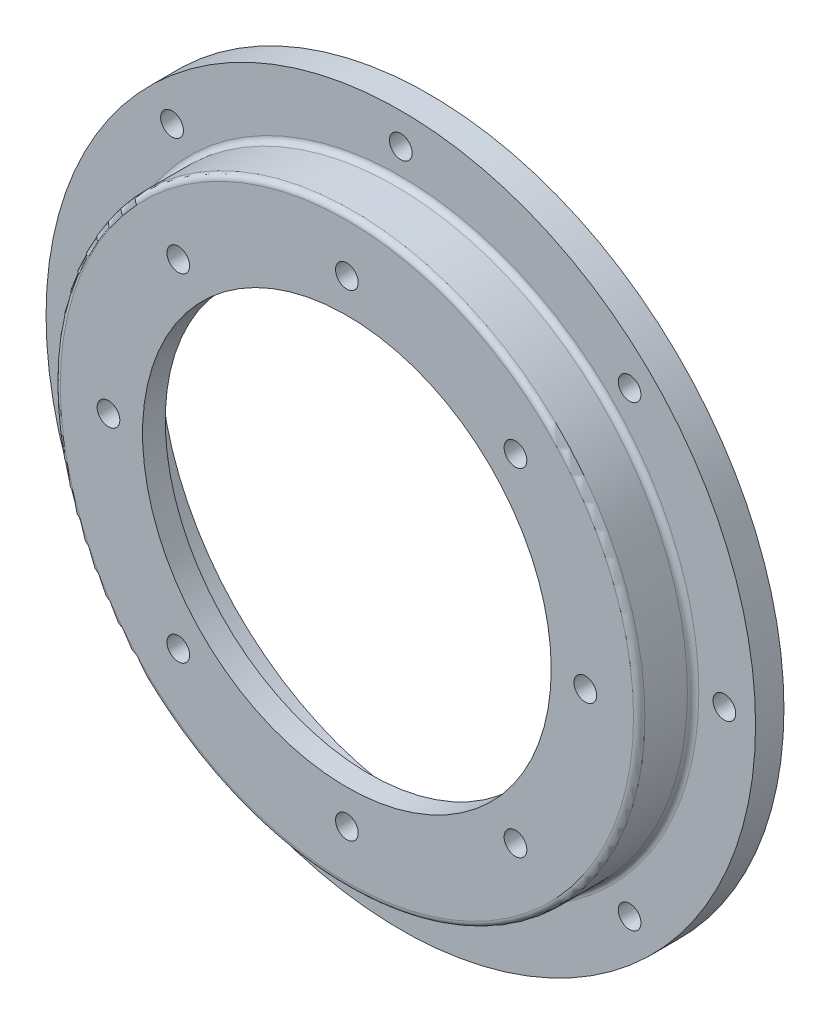
SolidWorks part; units mm, degrees
material "1.0503 (C45)"
ref_plane "Front Plane" through (0, 0, 0) normal (0, 0, 1) x (1, 0, 0)
ref_plane "Top Plane" through (0, 0, 0) normal (0, 1, 0) x (1, 0, 0)
ref_plane "Right Plane" through (0, 0, 0) normal (1, 0, 0) x (0, 0, -1)
sketch "Sketch1" plane through (0, 0, 0) normal (0, 0, 1) x (1, 0, 0)
  line L0 (0, 0) -> (0, 63.1981) construction
  circle A0 centre (0, 0) radius 62.5
  circle A1 centre (0, 0) radius 36
  circle A2 centre (0, 0) radius 51.5
  circle A3 centre (0, 0) radius 47.5
  point P2 (0, 57)
  point P3 (0, 42)
  point P5 (29.6985, 29.6985)
  point P6 (40.3051, 40.3051)
  point P8 (42, 0)
  point P9 (29.6985, -29.6985)
  point P10 (0, -42)
  point P11 (-29.6985, -29.6985)
  point P12 (-42, 0)
  point P13 (-29.6985, 29.6985)
  point P14 (0, 0)
  point P17 (57, 0)
  point P18 (40.3051, -40.3051)
  point P19 (0, -57)
  point P20 (-40.3051, -40.3051)
  point P21 (-57, 0)
  point P22 (-40.3051, 40.3051)
  point P23 (0, 0)
  dimension "D1" = 125
  dimension "D4" = 72
  dimension "D7" = 103
  dimension "D8" = 95
  dimension "D2" = 42
  dimension "D5" = 57
  dimension "D3" = 8
  dimension "D6" = 8
extrude "Boss-Extrude1" add sketch "Sketch1" along normal blind 5 contours A2 A0 | A3 A2 | A1 A3 region at (-60.7322, 0, 0) region at (-50.0434, 0, 0) region at (-46.1565, 0, 0)
sketch "Sketch4" plane through (0, 0, 0) normal (0, 0, 1) x (1, 0, 0)
  line L0 (0, 0) -> (0, 63.1981) construction
  circle A0 centre (0, 0) radius 62.5
  circle A1 centre (0, 0) radius 35
  circle A2 centre (0, 42) radius 5
  circle A3 centre (29.6985, 29.6985) radius 5
  circle A4 centre (42, 0) radius 5
  circle A5 centre (29.6985, -29.6985) radius 5
  circle A6 centre (0, -42) radius 5
  circle A7 centre (-29.6985, -29.6985) radius 5
  circle A8 centre (-42, 0) radius 5
  circle A9 centre (-29.6985, 29.6985) radius 5
  point P2 (0, 57)
  point P3 (0, 42)
  point P5 (29.6985, 29.6985)
  point P6 (40.3051, 40.3051)
  point P8 (42, 0)
  point P9 (29.6985, -29.6985)
  point P10 (0, -42)
  point P11 (-29.6985, -29.6985)
  point P12 (-42, 0)
  point P13 (-29.6985, 29.6985)
  point P14 (0, 0)
  point P17 (57, 0)
  point P18 (40.3051, -40.3051)
  point P19 (0, -57)
  point P20 (-40.3051, -40.3051)
  point P21 (-57, 0)
  point P22 (-40.3051, 40.3051)
  point P23 (0, 0)
  point P40 (0, 0)
  dimension "D1" = 125
  dimension "D4" = 70
  dimension "D7" = 8
  dimension "D8" = 10
  dimension "D2" = 42
  dimension "D5" = 57
  dimension "D3" = 8
  dimension "D6" = 8
extrude "Boss-Extrude2" add sketch "Sketch1<4>" along normal blind 14.5 contours A1 A3 | A3 A2 region at (-50.0434, 0, 0) region at (-46.1565, 0, 0)
sketch "Sketch1<4>" plane through (0, 0, 0) normal (0, 0, 1) x (1, 0, 0) same geometry as "Sketch1"
sketch "Sketch11" plane through (0, 0, 0) normal (0, 0, 1) x (1, 0, 0)
  line L0 (0, 0) -> (0, 63.1981) construction
  circle A0 centre (0, 0) radius 60
  circle A1 centre (0, 0) radius 36
  circle A2 centre (0, 0) radius 51.5
  circle A3 centre (0, 0) radius 47.5
  point P2 (0, 57)
  point P3 (0, 42)
  point P5 (29.6985, 29.6985)
  point P6 (40.3051, 40.3051)
  point P8 (42, 0)
  point P9 (29.6985, -29.6985)
  point P10 (0, -42)
  point P11 (-29.6985, -29.6985)
  point P12 (-42, 0)
  point P13 (-29.6985, 29.6985)
  point P14 (0, 0)
  point P17 (57, 0)
  point P18 (40.3051, -40.3051)
  point P19 (0, -57)
  point P20 (-40.3051, -40.3051)
  point P21 (-57, 0)
  point P22 (-40.3051, 40.3051)
  point P23 (0, 0)
  dimension "D1" = 120
  dimension "D4" = 72
  dimension "D7" = 103
  dimension "D8" = 95
  dimension "D2" = 42
  dimension "D5" = 57
  dimension "D3" = 8
  dimension "D6" = 8
hole_wizard "Ø4.0mm Dowel Hole3" positions "Sketch12" profile "Sketch13" hole size "Ø4.0" standard "ISO" end condition through all
sketch "Sketch12" plane through (0, 0, 0) normal (0, 0, -1) x (-1, 0, 0)
  line L0 (0, 0) -> (0, 62.1794)
  point P0 (0, 57)
  point P3 (0, 42)
  point P6 (40.3051, 40.3051)
  point P9 (29.6985, 29.6985)
  point P12 (42, 0)
  point P15 (57, 0)
  point P18 (40.3051, -40.3051)
  point P21 (29.6985, -29.6985)
  point P24 (0, -42)
  point P27 (0, -57)
  point P30 (-29.6985, -29.6985)
  point P33 (-40.3051, -40.3051)
  point P36 (-42, 0)
  point P39 (-57, 0)
  point P42 (-29.6985, 29.6985)
  point P45 (-40.3051, 40.3051)
sketch "Sketch13" plane through (0, 57, 0) normal (1, 0, 0) x (0, 1, 0)
  line L0 (0, 0) -> (0, 14.5)
  line L1 (0, 14.5) -> (2, 14.5)
  line L2 (2, 14.5) -> (2, 0.025)
  line L3 (2, 0.025) -> (2.025, 0)
  line L5 (2.025, 0) -> (0, 0)
  line L6 (-2, 0.025) -> (-2.025, 0) construction
  line L11 (0, -6.35) -> (0, 107.95) construction
  dimension "Thru Hole Dia." = 4
  dimension "Thru Hole Depth" = 14.5
  dimension "Near C'Sink Dia." = 4.05
  dimension "Near C'Sink Angle" = 90
sketch "Sketch7" plane through (0, 0, 0) normal (0, 0, 1) x (1, 0, 0)
  line L0 (0, 0) -> (0, 63.1981) construction
  circle A0 centre (0, 0) radius 60
  circle A1 centre (0, 0) radius 36
  point P2 (0, 57)
  point P3 (0, 42)
  point P5 (29.6985, 29.6985)
  point P6 (40.3051, 40.3051)
  point P8 (42, 0)
  point P9 (29.6985, -29.6985)
  point P10 (0, -42)
  point P11 (-29.6985, -29.6985)
  point P12 (-42, 0)
  point P13 (-29.6985, 29.6985)
  point P14 (0, 0)
  point P17 (57, 0)
  point P18 (40.3051, -40.3051)
  point P19 (0, -57)
  point P20 (-40.3051, -40.3051)
  point P21 (-57, 0)
  point P22 (-40.3051, 40.3051)
  point P23 (0, 0)
  dimension "D1" = 120
  dimension "D4" = 72
  dimension "D2" = 42
  dimension "D5" = 57
  dimension "D3" = 8
  dimension "D6" = 8
extrude "Cut-Extrude4" cut sketch "Sketch11" along normal blind 10.5 contours A1 A3 region at (-46.1565, 0, 0)
fillet "Fillet1" radius 1 3 edges at (47.5, 0, 10.5) (51.5, 0, 5) (51.5, 0, 14.5)
